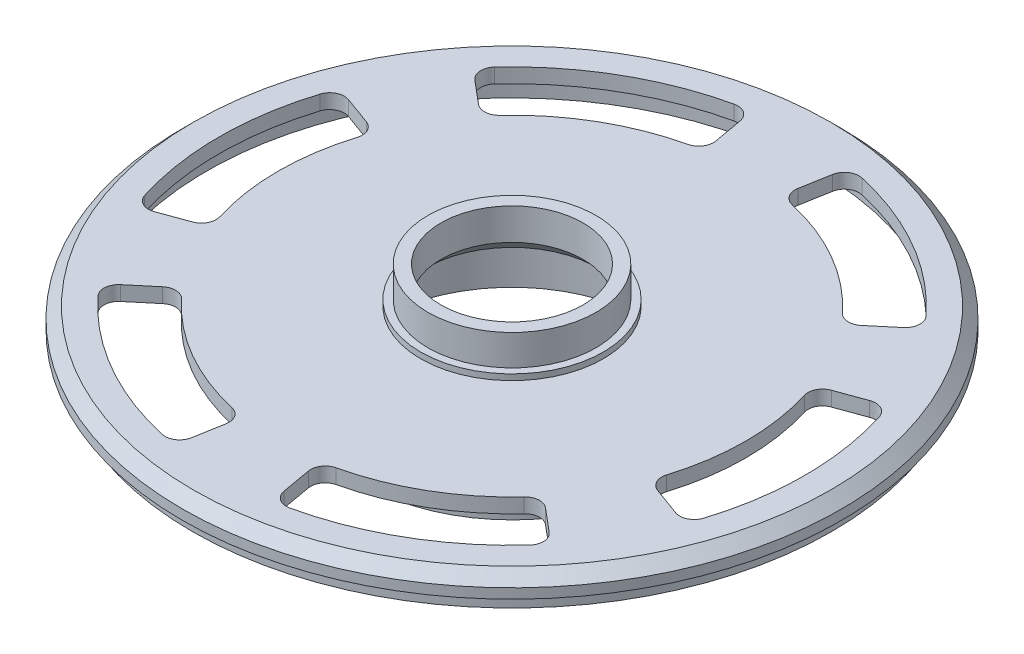
SolidWorks part; units mm, degrees
note: '?' marks a value the reader was unsure of.
ref_plane "Front Plane" through (0, 0, 0) normal (0, 0, 1) x (1, 0, 0)
ref_plane "Top Plane" through (0, 0, 0) normal (0, 1, 0) x (1, 0, 0)
ref_plane "Right Plane" through (0, 0, 0) normal (1, 0, 0) x (0, 0, -1)
ref_axis "Axis1" through (0, 0, 0) along (0, 1, 0)?
sketch "Sketch1" plane through (0, 0, 0) normal (0, 0, 1) x (1, 0, 0)
  line L0 (0, 0) -> (0, -50000) construction
  line L1 (-45.1, 8.15) -> (-43.75, 8.15)
  line L2 (45.1, 8.15) -> (-45.1, 8.15) construction
  line L3 (-43.75, 8.15) -> (-43.75, 6.15)
  line L4 (-43.75, 6.15) -> (-41.75, 6.15)
  line L5 (-41.75, 6.15) -> (-41.75, 9)
  line L6 (-41.75, 9) -> (-30.5, 9)
  line L7 (-45.1, 8.15) -> (-45.1, 9.5)
  line L8 (-43.6, 11) -> (-12.5, 11)
  line L9 (-43.8, 8.15) -> (-43.8, -6.15) construction
  line L10 (16.4229, 6.15) -> (7.6219, 6.15) construction
  line L11 (-20.5, 9) -> (-20.5, 0.15)
  line L12 (-20.5, 0.15) -> (-18.5, 0.15)
  line L13 (-18.5, 0.15) -> (-18.5, 8.15)
  line L15 (-9.73, 11.6734) -> (-9.73, 16)
  line L19 (39.5, 7.5) -> (-39.5, 7.5) construction
  line L20 (-18.5, 8.15) -> (-17.75, 8.15)
  line L23 (-11.5, 16) -> (-9.73, 16)
  line L24 (-17.75, 8.15) -> (-17.75, 9.65)
  line L25 (-17.75, 9.65) -> (-11.7534, 9.65)
  line L26 (18.25, 8.15) -> (-18.25, 8.15) construction
  line L27 (-30.5, 9) -> (-29.5, 7.5)
  line L28 (-29.5, 7.5) -> (-24.5, 7.5)
  line L29 (-24.5, 7.5) -> (-23.5, 9)
  line L30 (-23.5, 9) -> (-20.5, 9)
  line L31 (-11.7534, 9.65) -> (-9.73, 11.6734)
  line L41 (-45.1, 9.5) -> (-43.6, 11)
  line L43 (-12.5, 11) -> (-12.5, 11.8)
  line L44 (-12.5, 11.8) -> (-11.5, 11.8)
  line L45 (-9.23, 18.1) -> (-9.23, 5.85) construction
  line L46 (-11.5, 16) -> (-11.5, 11.8)
  line L47 (-18.25, 0.15) -> (18.25, 0.15) construction
  point P10 (-45.1, 11)
  point P35 (-27, 7.5)
  dimension "D1" = 0.05
  dimension "D2" = 2
  dimension "D3" = 2
  dimension "D4" = 2
  dimension "D5" = 27
  dimension "D6" = 1.5
  dimension "D7" = 0.75
  dimension "D8" = 4.2
  dimension "D9" = 1.5
  dimension "D10" = 135
  dimension "D11" = 0.5
  dimension "D12" = 5
  dimension "D13" = 7
  dimension "D14" = 1.5
  dimension "D15" = 0.8
  dimension "D16" = 1
  dimension "D19" = 23
  dimension "D20" = 37
revolve "Revolve1" add sketch "Sketch1" angle 360 about L0
sketch "Sketch2" plane through (0, 0, 0) normal (0, 1, 0) x (1, 0, 0)
  line L0 (0, 0) -> (50000, 0) construction
  line L1 (35.6692, 13.2833) -> (31.8121, 11.8794)
  line L2 (31.8121, -11.8794) -> (35.6692, -13.2833)
  arc A0 (38.2616, 12.0025) -> (38.2616, -12.0025) centre (0, 0) cw
  arc A1 (30.5846, 9.4118) -> (30.5846, -9.4118) centre (0, 0) cw
  arc A2 (38.2616, -12.0025) -> (35.6692, -13.2833) centre (36.3533, -11.4039) cw
  arc A3 (30.5846, -9.4118) -> (31.8121, -11.8794) centre (32.4962, -10) ccw
  arc A4 (38.2616, 12.0025) -> (35.6692, 13.2833) centre (36.3533, 11.4039) ccw
  arc A5 (30.5846, 9.4118) -> (31.8121, 11.8794) centre (32.4962, 10) cw
  circle A8 centre (0, 0) radius 45.1 construction
  point P11 (37.5841, -13.9802)
  point P14 (29.9723, -11.2098)
  point P17 (37.5841, 13.9802)
  point P20 (29.9723, 11.2098)
  dimension "D1" = 2
  dimension "D3" = 5
  dimension "D5" = 32
  dimension "D2" = 40
  dimension "D4" = 20
extrude "Cut-Extrude1" cut sketch "Sketch2" along normal through all and the other way through all
pattern_circular "CirPattern1" count 6 over 360 about axis through (0, 0, 0) along (0, 1, 0) of "Cut-Extrude1"
sketch "Sketch3" plane through (0, 0, 0) normal (0, 0, 1) x (1, 0, 0)
  line L0 (0, 0) -> (0, -50000) construction
  line L1 (-24.6984, 10) -> (-28.6984, 10) construction
  line L2 (-29.1, 10) -> (-24.9, 10)
  line L3 (-29.1, 10) -> (-29.1, 7.2084)
  line L4 (-29.1, 7.2084) -> (-24.9, 7.2084)
  line L5 (-24.9, 10) -> (-24.9, 7.2084)
  point P7 (-27, 10)
  dimension "D1" = 27
  dimension "D2" = 4.2
revolve "Cut-Revolve1" [suppressed] cut sketch "Sketch3" angle 360 about L0
sketch "Sketch4" plane through (0, 0, 0) normal (0, 1, 0) x (1, 0, 0)
  circle A0 centre (27, 0) radius 2.06
  dimension "D1" = 4.12
  dimension "D2" = 27
extrude "Cut-Extrude3" cut sketch "Sketch4" against normal through all from surface at 10
pattern_circular "CirPattern2" count 42 over 360 about axis through (0, 0, 0) along (0, 1, 0) of "Cut-Extrude3"
sketch "Sketch5" plane through (0, 7.5, 0) normal (0, -1, 0) x (1, 0, 0)
  circle A0 centre (0, 0) radius 27
extrude "Cut-Extrude-Thin1" cut sketch "Sketch5" against normal up to surface (2.5 mm away) thin thin type mid plane wall 2.5
